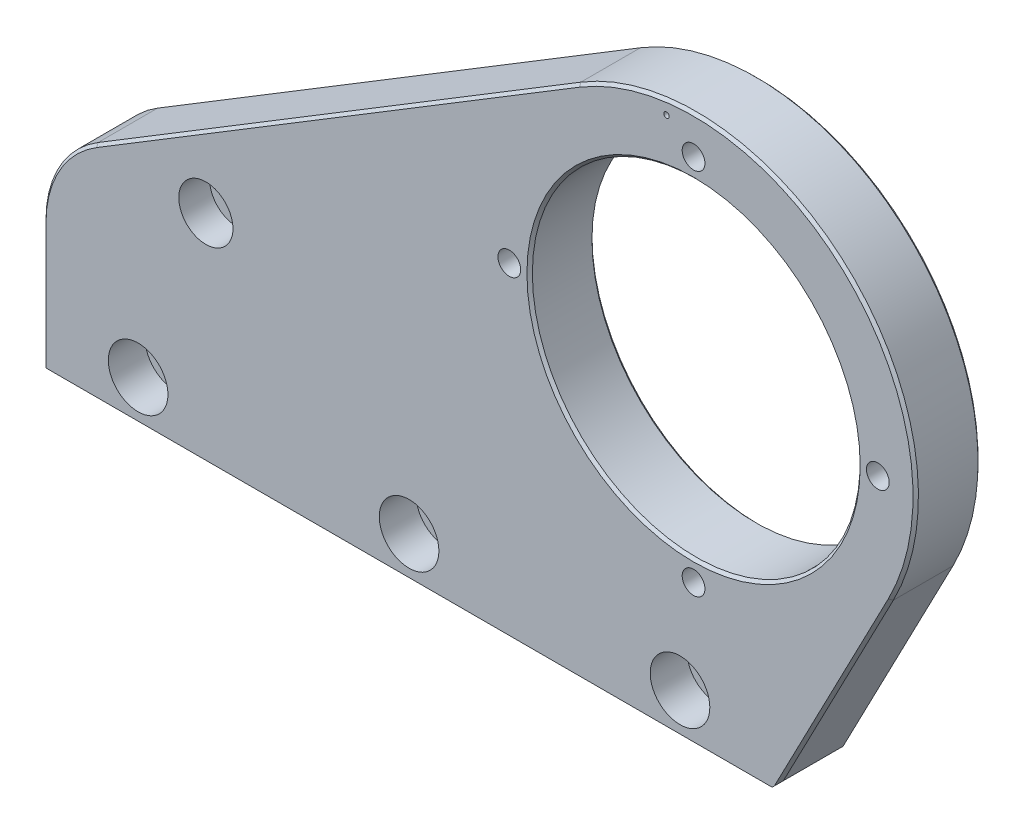
SolidWorks part; units mm, degrees
material "45"
ref_plane "前视基准面" through (0, 0, 0) normal (0, 0, 1) x (1, 0, 0)
ref_plane "上视基准面" through (0, 0, 0) normal (0, 1, 0) x (1, 0, 0)
ref_plane "右视基准面" through (0, 0, 0) normal (1, 0, 0) x (0, 0, -1)
sketch "草图1" plane through (0, 0, 0) normal (0, 0, 1) x (1, 0, 0)
  line L1 (-120, -36.2443) -> (-120, -60)
  line L3 (-110.3932, -19.1568) -> (-21.3061, 35.0293)
  line L4 (-120, -60) -> (15, -60)
  line L5 (15, -60) -> (36.3716, -18.9238)
  arc A0 (36.3716, -18.9238) -> (-21.3061, 35.0293) centre (0, 0) ccw
  arc A1 (-120, -36.2443) -> (-110.3932, -19.1568) centre (-100, -36.2443) cw
  point P4 (-120, -25)
  dimension "D5" = 60
  dimension "D7" = 41
  dimension "D4" = 20
  dimension "D1" = 135
  dimension "D2" = 35
  dimension "D3" = 120
extrude "凸台-拉伸1" add sketch "草图1" along normal blind 12
sketch "草图2" plane through (0, 0, 12) normal (0, 0, 1) x (1, 0, 0)
  circle A0 centre (0, 0) radius 30.25
  dimension "D1" = 60.5
extrude "切除-拉伸1" cut sketch "草图2" against normal blind 38
sketch "草图3" plane through (0, 0, 12) normal (0, 0, 1) x (1, 0, 0)
  line L0 (-34, 0) -> (0, -34)
  line L1 (-34, 0) -> (0, 34)
  line L2 (0, -34) -> (34, 0)
  line L3 (0, 34) -> (34, 0)
  line L4 (-34, 0) -> (34, 0) construction
  line L5 (0, -34) -> (0, 34) construction
  point P1 (0, 0)
  dimension "D1" = 68
hole_wizard "M5 螺纹孔1" positions "3D草图1" profile "草图4" tap size "M5" standard "Gb"
sketch3d "3D草图1"
  point P0 (0, 34, 12)
  point P3 (34, 0, 12)
  point P6 (-34, 0, 12)
  point P9 (0, -34, 12)
sketch "草图4" plane through (0, 34, 12) normal (1, 0, 0) x (0, -1, 0)
  line L0 (0, 0) -> (0, 33.6618)
  line L1 (0, 33.6618) -> (2.1, 32.4)
  line L2 (2.1, 32.4) -> (2.1, 0)
  line L5 (2.1, 0) -> (0, 0)
  line L10 (0, 33.6618) -> (-2.1, 32.4) construction
  line L11 (0, -6.35) -> (0, 107.95) construction
  dimension "螺纹孔钻头直径" = 4.2
  dimension "螺纹孔钻头深度" = 32.4
  dimension "导头角度" = 118
cosmetic thread "孔螺蚊线1" parameters "D1"=10, "D2"=5
cosmetic thread "孔螺蚊线2" parameters "D1"=10, "D2"=5
cosmetic thread "孔螺蚊线3" parameters "D1"=10, "D2"=5
cosmetic thread "孔螺蚊线4" parameters "D1"=10, "D2"=5
sketch "草图12" plane through (0, 0, 12) normal (0, 0, 1) x (1, 0, 0)
  line L0 (-52.5, -60) -> (-52.5, 94.3335) construction
  line L1 (-120, -60) -> (15, -60) construction
  line L2 (-120, -60) -> (15, -60) construction
  point P0 (-102.5, -52.5)
  point P1 (-52.5, -52.5)
  point P2 (-2.5, -52.5)
  dimension "D1" = 7.5
  dimension "D2" = 50
  dimension "D3" = 50
hole_wizard "打孔尺寸根据内六角圆柱头螺钉的类型2" positions "3D草图5" profile "草图13" counterbore size "M6" standard "Gb" end condition through all
sketch3d "3D草图5"
  point P0 (-102.5, -52.5, 12)
  point P3 (-52.5, -52.5, 12)
  point P6 (-2.5, -52.5, 12)
sketch "草图13" plane through (-102.5, -52.5, 12) normal (1, 0, 0) x (0, -1, 0)
  line L0 (0, 0) -> (0, 12)
  line L1 (0, 12) -> (3.3, 12)
  line L3 (3.3, 12) -> (3.3, 6.8)
  line L4 (3.3, 6.8) -> (5.5, 6.8)
  line L5 (5.5, 6.8) -> (5.5, 0)
  line L7 (5.5, 0) -> (0, 0)
  line L11 (0, -6.35) -> (0, 107.95) construction
  dimension "通孔孔直径" = 6.6
  dimension "通孔孔深度" = 12
  dimension "柱形沉头孔直径" = 11
  dimension "柱形沉头孔深度" = 6.8
sketch "草图14" plane through (0, 0, 12) normal (0, 0, 1) x (1, 0, 0)
  line L0 (-120, -60) -> (15, -60) construction
  point P0 (-90, -20)
  dimension "D1" = 40
  dimension "D2" = 90
hole_wizard "打孔尺寸根据内六角圆柱头螺钉的类型3" positions "3D草图6" profile "草图15" counterbore size "M5" standard "Gb" end condition through all
sketch3d "3D草图6"
  point P0 (-90, -20, 12)
sketch "草图15" plane through (-90, -20, 12) normal (1, 0, 0) x (0, -1, 0)
  line L0 (0, 0) -> (0, 12)
  line L1 (0, 12) -> (2.75, 12)
  line L3 (2.75, 12) -> (2.75, 5.7)
  line L4 (2.75, 5.7) -> (5, 5.7)
  line L5 (5, 5.7) -> (5, 0)
  line L7 (5, 0) -> (0, 0)
  line L11 (0, -6.35) -> (0, 107.95) construction
  dimension "通孔孔直径" = 5.5
  dimension "通孔孔深度" = 12
  dimension "柱形沉头孔直径" = 10
  dimension "柱形沉头孔深度" = 5.7
sketch "草图16" plane through (0, 0, 0) normal (0, 0, -1) x (-1, 0, 0)
  circle A0 centre (5, 38.1739) radius 0.5
  circle A1 centre (0, 0) radius 38.5 construction
  circle A2 centre (-5, 38.1739) radius 1.1823 construction
  dimension "D1" = 1
  dimension "D2" = 10
  dimension "D4" = 77
extrude "切除-拉伸2" cut sketch "草图16" against normal through all
chamfer "倒角1" distance 1 angle 45 2 edges at (-120, -60, 6) (15, -60, 6) first distance on face at (-52.5, -60, 6)
chamfer "倒角2" distance 0.5 angle 45 2 edges at (30.25, 0, 12) (-30.25, 0, 0)
chamfer "倒角3" distance 0.5 angle 45 11 edges at (-52.5, -60, 12) (-120, -47.6221, 12) (-117.4337, -26.4428, 12) (26.2281, -38.4196, 12) (28.0085, 29.942, 12) (-65.8497, 7.9362, 12) (26.2281, -38.4196, 0) (28.0085, 29.942, 0) (-120, -47.6221, 0) (-117.4337, -26.4428, 0) (-65.8497, 7.9362, 0)
